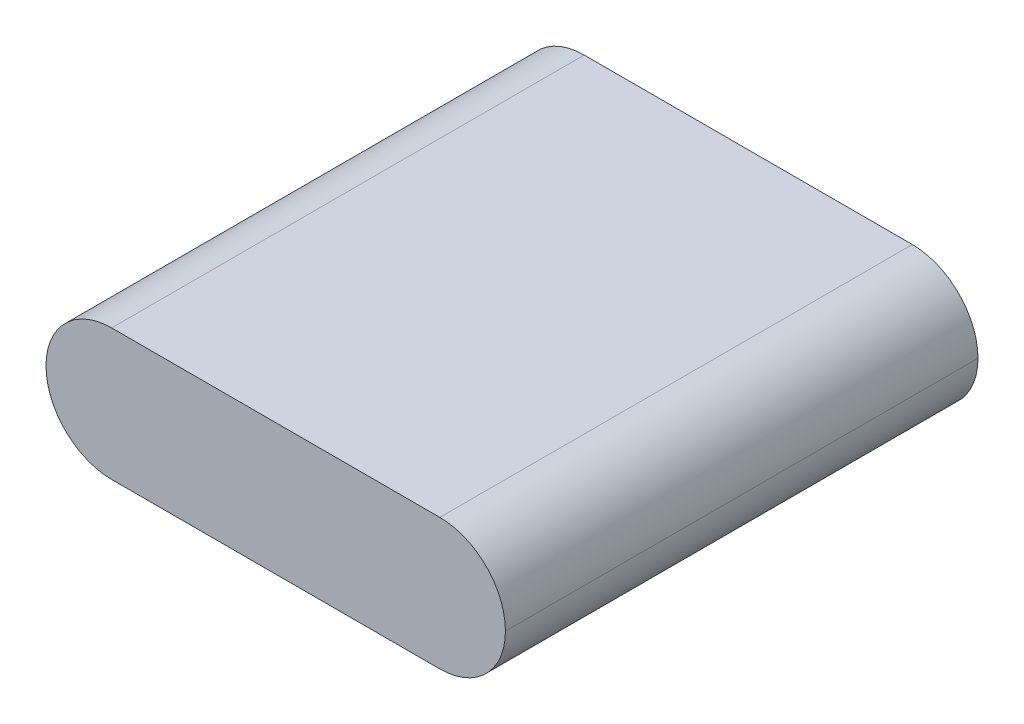
SolidWorks part; units mm, degrees
ref_plane "Front" through (0, 0, 0) normal (0, 0, 1) x (1, 0, 0)
ref_plane "Top" through (0, 0, 0) normal (0, 1, 0) x (1, 0, 0)
ref_plane "Right" through (0, 0, 0) normal (1, 0, 0) x (0, 0, -1)
sketch "Sketch1" plane through (0, 0, 0) normal (0, 1, 0) x (1, 0, 0)
  line L1 (0, 0) -> (70, 0)
  line L2 (0, 0) -> (0, 72)
  line L3 (0, 72) -> (70, 72)
  line L4 (70, 0) -> (70, 72)
  dimension "D1" = 72
  dimension "D2" = 70
extrude "Boss-Extrude1" add sketch "Sketch1" along normal blind 20
fillet "Fillet1" radius 10 4 edges at (0, 0, -36) (70, 0, -36) (70, 20, -36) (0, 20, -36)
